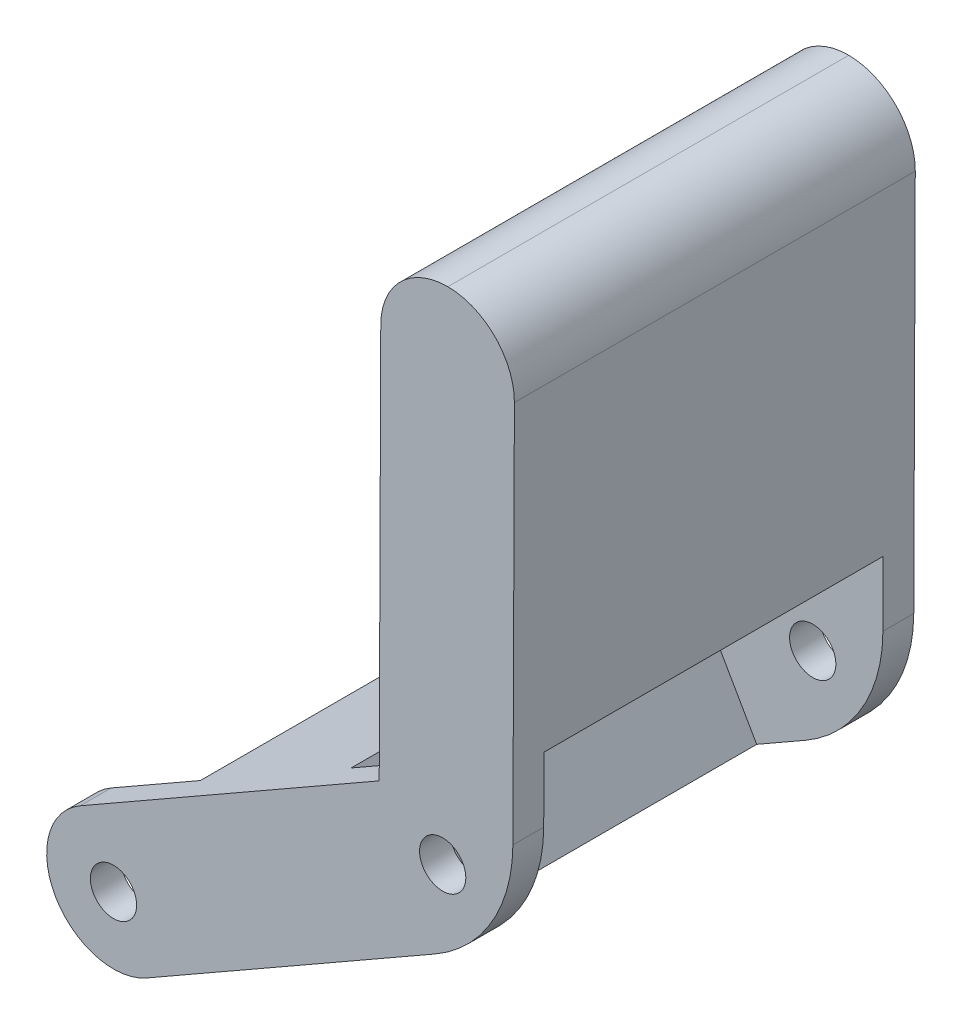
SolidWorks part; units mm, degrees
ref_plane "Plano frontal" through (0, 0, 0) normal (0, 0, 1) x (1, 0, 0)
ref_plane "Plano superior" through (0, 0, 0) normal (0, 1, 0) x (1, 0, 0)
ref_plane "Plano direito" through (0, 0, 0) normal (1, 0, 0) x (0, 0, -1)
sketch "Sketch1" plane through (0, 0, 0) normal (0, 0, 1) x (1, 0, 0)
  line L0 (7.1019, 0.1274) -> (7.3089, 52.6325)
  line L1 (7.3089, 52.6325) -> (-5.691, 52.6838)
  line L2 (-5.691, 52.6838) -> (-5.8684, 7.6841)
  line L3 (-5.8684, 7.6841) -> (-40.588, -12.1792)
  line L4 (-40.588, -12.1792) -> (-34.1324, -23.463)
  line L5 (-34.1324, -23.463) -> (7.1019, 0.1274)
  line L6 (-5.8684, 7.6841) -> (7.1019, 0.1274) construction
  circle A0 centre (-31.7183, -14.5933) radius 2.25
  circle A1 centre (0.307, 3.7285) radius 2.25
  dimension "D5" = 4.5
  dimension "D6" = 6.5
  dimension "D7" = 4.5
  dimension "D10" = 6.5
  dimension "D9" = 6.5
  dimension "D1" = 13
  dimension "D2" = 13
  dimension "D3" = 45
  dimension "D4" = 40
  dimension "D8" = 120
extrude "Boss-Extrude1" add sketch "Sketch1" along normal blind 39
sketch "Sketch2" plane through (1.6964, -2.9652, 0) normal (0.4966, -0.868, 0) x (0.868, 0.4966, 0)
  line L0 (-41.2779, 39) -> (-41.2779, 0) construction
  line L1 (-41.2779, 36) -> (13.7221, 36)
  line L2 (-41.2779, 36) -> (-41.2779, 3)
  line L3 (-41.2779, 3) -> (13.7221, 3)
  line L4 (13.7221, 36) -> (13.7221, 3)
  line L5 (-41.2779, 39) -> (6.2276, 39) construction
  line L6 (-41.2779, 0) -> (6.2276, 0) construction
  dimension "D1" = 3
  dimension "D2" = 3
  dimension "D3" = 55
extrude "Cut-Extrude1" cut sketch "Sketch2" against normal through all
fillet "Fillet1" radius 6.5 4 edges at (-34.1324, -23.463, 1.5) (-40.588, -12.1792, 1.5) (-34.1324, -23.463, 37.5) (-40.588, -12.1792, 37.5)
fillet "Fillet2" radius 15 2 edges at (7.1019, 0.1274, 37.5) (7.1019, 0.1274, 1.5)
sketch "Sketch3" plane through (0, 0, 3) normal (0, 0, 1) x (1, 0, 0)
  line L0 (-26.2662, -3.9856) -> (-19.8106, -15.2694)
  line L1 (-5.8684, 7.6841) -> (-34.9461, -8.9514) construction
  line L2 (-28.4905, -20.2353) -> (-0.4151, -4.1732) construction
  line L3 (-19.8106, -15.2694) -> (-5.1452, -6.8792)
  line L4 (-5.1452, -6.8792) -> (-11.6007, 4.4046)
  line L5 (-11.6007, 4.4046) -> (-26.2662, -3.9856)
  circle A0 centre (-31.7183, -14.5933) radius 2.25 construction
  circle A1 centre (0.307, 3.7285) radius 2.25 construction
  dimension "D1" = 10
  dimension "D2" = 10
extrude "Boss-Extrude2" add sketch "Sketch3" along normal up to next
fillet "Fillet3" radius 6.5 2 edges at (7.3089, 52.6325, 19.5) (-5.691, 52.6838, 19.5)
